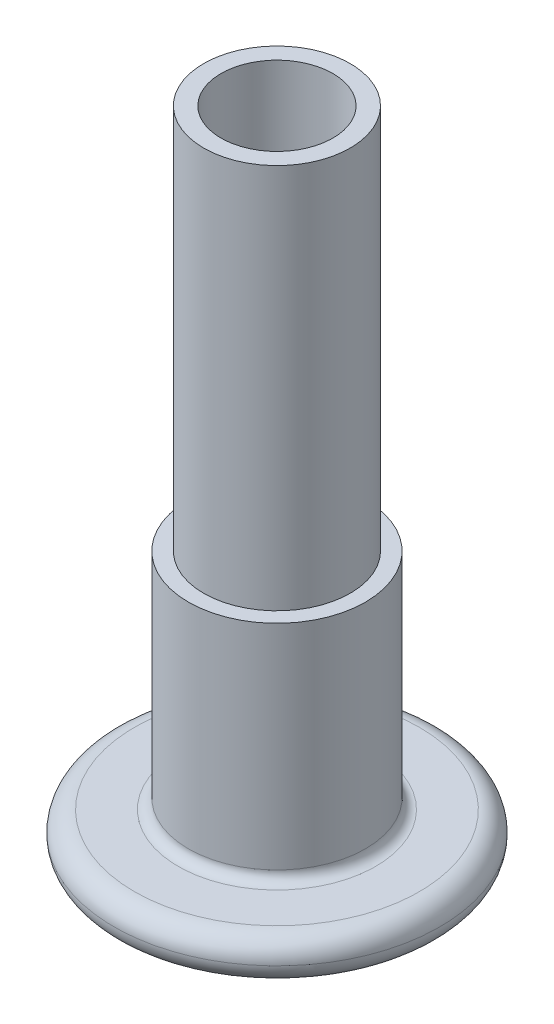
SolidWorks part; units mm, degrees
ref_plane "Front Plane" through (0, 0, 0) normal (0, 0, 1) x (1, 0, 0)
ref_plane "Top Plane" through (0, 0, 0) normal (0, 1, 0) x (1, 0, 0)
ref_plane "Right Plane" through (0, 0, 0) normal (1, 0, 0) x (0, 0, -1)
sketch "Sketch1" plane through (0, 0, 0) normal (0, 1, 0) x (1, 0, 0)
  circle A0 centre (0, 0) radius 8.7
  circle A1 centre (0, 0) radius 5.5
  dimension "D1" = 17.4
  dimension "D3" = 11
extrude "Boss-Extrude1" add sketch "Sketch1" along normal blind 68.8
sketch "Sketch2" plane through (0, 0, 0) normal (0, -1, 0) x (1, 0, 0)
  circle A0 centre (0, 0) radius 5.5
  circle A1 centre (0, 0) radius 16
  dimension "D1" = 32
extrude "Boss-Extrude2" add sketch "Sketch2" along normal blind 4
fillet "Fillet1" radius 2 2 edges at (0, -4, -16) (0, 0, -16)
fillet "Fillet2" radius 1 1 edges at (0, 0, -8.7)
sketch "Sketch7" plane through (0, 68.8, 0) normal (0, 1, 0) x (1, 0, 0)
  line L0 (0, 0) -> (0, 11.5063) construction
  line L1 (0, 0) -> (9.9648, -5.7532) construction
  line L2 (0, 0) -> (-8.8335, -5.1) construction
  line L9 (-8.4598, -2.0303) -> (-9.806, -2.8076)
  line L11 (-5.9882, -6.3112) -> (-7.3314, -7.0915)
  line L12 (-2.4716, 8.3415) -> (-2.4757, 9.895)
  line L19 (2.4716, 8.3415) -> (2.4757, 9.895)
  line L20 (8.4598, -2.0303) -> (9.8072, -2.8035)
  line L21 (5.9882, -6.3112) -> (7.3314, -7.0915)
  arc A0 (-8.4598, -2.0303) -> (-5.9882, -6.3112) centre (0, 0) ccw
  arc A1 (-9.806, -2.8076) -> (-7.3314, -7.0915) centre (0, 0) ccw
  arc A2 (2.4716, 8.3415) -> (-2.4716, 8.3415) centre (0, 0) ccw
  arc A3 (2.4757, 9.895) -> (-2.4757, 9.895) centre (0, 0) ccw
  arc A4 (5.9882, -6.3112) -> (8.4598, -2.0303) centre (0, 0) ccw
  arc A5 (7.3314, -7.0915) -> (9.8072, -2.8035) centre (0, 0) ccw
  point P5 (2.5, 0)
  point P6 (2.5, 11.5063)
  point P8 (-9.9648, -5.7532)
  point P10 (-1.25, 2.1651)
  point P11 (-11.2148, -3.5881)
  point P12 (-1.25, -2.1651)
  point P13 (8.7148, -7.9182)
  point P14 (-2.5, 0)
  point P15 (-2.5, 11.5063)
  point P16 (1.25, -2.1651)
  point P17 (-8.7148, -7.9182)
  point P18 (1.25, 2.1651)
  point P19 (11.2148, -3.5881)
  dimension "D2" = 17.4
  dimension "D3" = 1.5
  dimension "D1" = 3
extrude "Boss-Extrude6" add sketch "Sketch7" against normal blind 10
ref_plane "Plane1" through (0, 45, 0) normal (0, 1, 0) x (1, 0, 0)
sketch "Sketch10" plane through (0, 45, 0) normal (0, 1, 0) x (1, 0, 0)
  circle A0 centre (0, 0) radius 8.7
  circle A1 centre (0, 0) radius 7.2
  dimension "D2" = 17.4
extrude "Cut-Extrude1" cut sketch "Sketch10" against normal blind 23
sketch "Sketch11" plane through (0, 45, 0) normal (0, -1, 0) x (1, 0, 0)
  circle A0 centre (0, 0) radius 17.4281
extrude "Cut-Extrude2" cut sketch "Sketch11" against normal through all
sketch "Sketch12" plane through (0, 45, 0) normal (0, 1, 0) x (1, 0, 0)
  circle A0 centre (0, 0) radius 5.5
  circle A1 centre (0, 0) radius 7.2
  dimension "D1" = 14.4
extrude "Boss-Extrude7" add sketch "Sketch12" along normal blind 14.9
equation "\"clearance\"= 0.3mm ' Freely and easily sliding. Used as a gap between the telescopic sections."
equation "\"clearance2\" = 0.1mm ' Used as a gap between rings next to each other."
equation "\"interference\"= 0.1mm ' This is like clearance1 but when two parts should just fit together rather than freely spin."
equation "\"D1@Sketch1\"=18.00mm-\"clearance\"*2"
equation "\"pegLength\"= 1.5mm ' The length of the pegs that stick out from the telescopic sections."
equation "\"D2@Sketch7\"=18.00mm-\"clearance\"*2"
equation "\"D3@Sketch7\"=\"pegLength\""
equation "\"D2@Sketch10\"=18.00mm-\"clearance\"*2"
equation "\"D1@Sketch12\"=18.00mm-\"clearance\"*2-3"
equation "\"D1@Boss-Extrude7\"=15.00mm - \"interference\""
